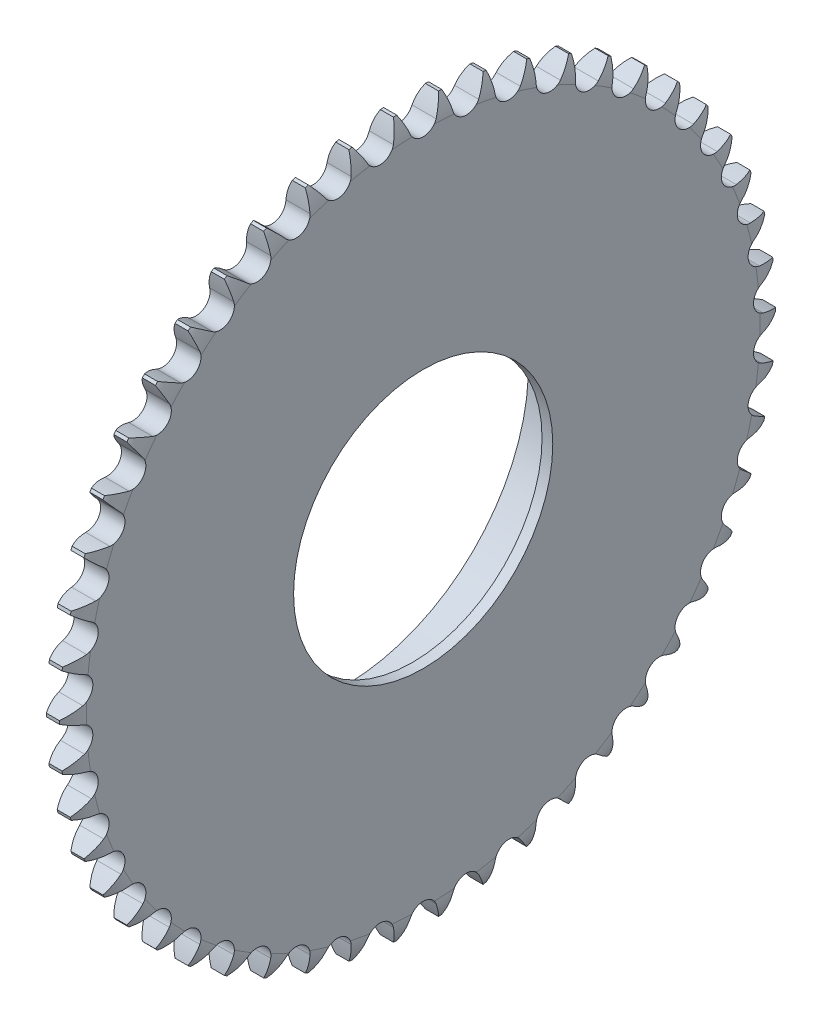
SolidWorks part; units mm, degrees
ref_plane "Plane1" through (0, 0, 0) normal (0, 0, 1) x (1, 0, 0)
ref_plane "Plane2" through (0, 0, 0) normal (0, 1, 0) x (1, 0, 0)
ref_plane "Plane3" through (0, 0, 0) normal (1, 0, 0) x (0, 0, -1)
sketch "Clipboard" plane through (0, 0, 0) normal (0, 1, 0) x (1, 0, 0)
  line L0 (0, 0) -> (10.2043, -12.161)
  line L1 (-15, 0) -> (100, 0) construction
  line L2 (0, 0) -> (-1.3675, 1.5456)
  line L3 (0, 0) -> (-14.8288, 5.6677)
  line L4 (0, 0) -> (1.9926, 2.3747)
  line L5 (0, 0) -> (-23.4238, -8.7364)
  line L6 (0, 0) -> (-7.4026, -4.9946)
  line L7 (-1.3675, 1.5456) -> (14.3658, 20.9747)
  line L8 (-76.2, 38.1) -> (-69.8, 38.1)
  line L9 (-73.5462, 42.5082) -> (-72.9534, 42.6013)
  line L10 (-74, 16.6356) -> (-55.89, 16.6356)
  circle A0 centre (0, 0) radius 5.08
  circle A1 centre (0, 0) radius 60
  circle A2 centre (0, 0) radius 60
  dimension "Num_teeth" = 50
  dimension "Thickness" = 8.93
sketch "BasProSke" plane through (0, 0, 0) normal (0, 1, 0) x (1, 0, 0)
  line L0 (-10, 0) -> (60, 0) construction
  line L1 (0, 0) -> (0, 123.4271)
  line L2 (0, 0) -> (8.93, 0)
  line L3 (8.93, 0) -> (8.93, 123.4271)
  line L4 (6.8662, 131.2543) -> (2.0637, 131.2543)
  arc A0 (0, 123.4271) -> (2.0637, 131.2543) centre (15.875, 123.4271) cw
  arc A1 (8.93, 123.4271) -> (6.8662, 131.2543) centre (-6.945, 123.4271) ccw
  dimension "D1" = 15.875
  dimension "Thickness" = 8.93
  dimension "Diameter" = 262.5085
revolve "Base-Revolve" add sketch "BasProSke" angle 360 about L0
sketch "TooCutSke" plane through (0, 0, 0) normal (1, 0, 0) x (0, 0, -1)
  line L0 (0, 126.4632) -> (4.7932, 124.6328) construction
  line L1 (0, 0) -> (0, 107) construction
  line L2 (0, 126.4632) -> (-10, 126.4632) construction
  line L3 (0, 126.4632) -> (-4.7932, 124.6328) construction
  arc A0 (4.7932, 124.6328) -> (7.9038, 131.517) centre (64.0203, 102.0162) cw
  arc A1 (4.7932, 124.6328) -> (-4.7932, 124.6328) centre (0, 126.4632) cw
  arc A2 (-4.7932, 124.6328) -> (-7.9038, 131.517) centre (-64.0203, 102.0162) ccw
  arc A3 (7.9038, 131.517) -> (-7.9038, 131.517) centre (0, 0) ccw
extrude "ToothCut" cut sketch "TooCutSke" along normal through all
pattern_circular "TeethCuts" count 50 every 7.2 about axis through (-10, 0, 0) along (1, 0, 0) of "ToothCut"
sketch "HubNeaOneSke" plane through (0, 0, 0) normal (-1, 0, 0) x (0, 0, 1)
  circle A0 centre (0, 0) radius 75
  dimension "D1" = 150
extrude "HubNearOne" add sketch "HubNeaOneSke" along normal blind 20
fillet "HubNearOneFillet" radius 0.6 1 edges at (0, 0, -75)
sketch "HubNeaBotSke" plane through (0, 0, 0) normal (-1, 0, 0) x (0, 0, 1)
  circle A0 centre (0, 0) radius 60
  dimension "Diameter" = 120
extrude "HubNearBoth" [suppressed] add sketch "HubNeaBotSke" along normal blind 8.0352
fillet "HubNearBothFillet" [suppressed] radius 0.6
ref_plane "FarPln" through (8.93, 0, 0) normal (1, 0, 0) x (0, 0, -1)
sketch "HubFarSke" plane through (8.93, 0, 0) normal (1, 0, 0) x (0, 0, -1)
  circle A0 centre (0, 0) radius 60
  dimension "Diameter" = 120
extrude "HubFar" [suppressed] add sketch "HubFarSke" along normal blind 8.0352
fillet "HubFarFillet" [suppressed] radius 0.6
sketch "BorSke" plane through (0, 0, 0) normal (1, 0, 0) x (0, 0, -1)
  circle A0 centre (0, 0) radius 47.5
  dimension "Diameter" = 95
extrude "Bore" cut sketch "BorSke" along normal mid plane 50.001
sketch "KeySke" plane through (0, 0, 0) normal (1, 0, 0) x (0, 0, -1)
  line L0 (-14, 0) -> (-14, 53.9)
  line L1 (-14, 53.9) -> (14, 53.9)
  line L2 (14, 53.9) -> (14, 0)
  line L3 (0, 0) -> (0, 34) construction
  line L4 (-14, 0) -> (14, 0)
  dimension "Width" = 28
extrude "Keyway" [suppressed] cut sketch "KeySke" along normal mid plane 50.001
pattern_circular "Keyway2" [suppressed] count 2 every 90 about axis through (-10, 0, 0) along (1, 0, 0) reverse direction yes
sketch "Schizzo1" plane through (-20, 0, 0) normal (-1, 0, 0) x (0, 0, 1)
  circle A0 centre (0, 0) radius 67.5
extrude "Taglio-Estrusione1" cut sketch "Schizzo1" against normal blind 25
equation "' \"Pitch@Clipboard\" = 12.7"
equation "' \"Num_strands@Clipboard\" = 1"
equation "' \"Num_teeth@Clipboard\" = 9"
equation "' \"Hub_dia@Clipboard\" = 50"
equation "' \"Overall_len@Clipboard\" = 3"
equation "' \"Diameter@BorSke\" = 12"
equation "' \"T_dim@Clipboard\" = 1"
equation "' \"Width@KeySke\" = 2"
equation "' \"Dr@Clipboard\" = 8.51"
equation "' \"Face_width@Clipboard\" = 7.2"
equation "' \"Side_radius@Clipboard\" = 12.7"
equation "' \"Side_relief@Clipboard\" = 1.27"
equation "' \"Transv_pitch@Clipboard\" = 13.92"
equation "' \"Show_teeth@Clipboard\" = 9"
equation "' \"Fillet_rad@Clipboard\" = 0.6"
equation "' \"Plate_wid@Clipboard\" = 11.8"
equation "\"Num_teeth@Clipboard\" = int( \"Num_teeth@Clipboard\" )"
equation "\"Num_teeth@Clipboard\" = ((sgn( \"Num_teeth@Clipboard\" - 5.0)+1)*( \"Num_teeth@Clipboard\" - 5.0))/2 +5.0"
equation "\"Num_teeth@Clipboard\" = ((sgn( \"Num_teeth@Clipboard\" - 200.0)-1)*( \"Num_teeth@Clipboard\" - 200.0))/-2 +200.0"
equation "\"MHD@Clipboard\" = \"Pitch@Clipboard\" * (1.0 / tan(3.14159265 / \"Num_teeth@Clipboard\" )) - 1.04 * \"Plate_wid@Clipboard\" - 0.76"
equation "\"Thickness@Clipboard\"  = \"Face_width@Clipboard\" + (\"Num_strands@Clipboard\" - 1) * \"Transv_pitch@Clipboard\""
equation "\"OAL@Clipboard\" = \"Thickness@Clipboard\" + 2 * \"Fillet_rad@Clipboard\" + 1"
equation "\"MHD@Clipboard\" = ((sgn( \"MHD@Clipboard\" - \"Hub_dia@Clipboard\" )-1)*( \"MHD@Clipboard\" - \"Hub_dia@Clipboard\" ))/-2+ \"Hub_dia@Clipboard\""
equation "\"OAL@Clipboard\" = ((sgn( \"OAL@Clipboard\" - \"Overall_len@Clipboard\" )+1)*( \"OAL@Clipboard\" - \"Overall_len@Clipboard\" ))/2 + \"Overall_len@Clipboard\" + 0.0005"
equation "\"Num_teeth@TeethCuts\" = int( \"Show_teeth@Clipboard\" ) + 1"
equation "\"Num_teeth@TeethCuts\" = ((sgn( \"Num_teeth@TeethCuts\" - \"Num_teeth@Clipboard\" )-1)*( \"Num_teeth@TeethCuts\" - \"Num_teeth@Clipboard\" ))/-2+ \"Num_teeth@Clipboard\""
equation "\"Num_teeth@TeethCuts\" = ((sgn( \"Num_teeth@TeethCuts\" - 2.0)+1)*( \"Num_teeth@TeethCuts\" - 2.0))/2 +2.0"
equation "\"Angle@TeethCuts\" = 360.0 / \"Num_teeth@Clipboard\""
equation "\"Seat_radius@TooCutSke\" = ( \"Pitch@Clipboard\" / 2.0) / sin(3.14159265 / \"Num_teeth@Clipboard\" ) - \"Dr@Clipboard\" / 2.0 + \"Dr@Clipboard\" * 0.505"
equation "\"R1@TooCutSke\"  = \"Dr@Clipboard\" * 0.505"
equation "\"X@TooCutSke\" = 140.0 - (90.0 / \"Num_teeth@Clipboard\")"
equation "\"R2@TooCutSke\" = 0.12 * \"Dr@Clipboard\" * ( \"Num_teeth@Clipboard\" + 2.0)"
equation "\"Overcut@TooCutSke\" = 0.5 + 0.625 * \"Pitch@Clipboard\" - 0.5 * \"Dr@Clipboard\"  +  \"Pitch@Clipboard\" / 2.0 / sin(3.14159265 / \"Num_teeth@Clipboard\" )"
equation "\"Diameter@BasProSke\" = 2.0 * ( 0.625 * \"Pitch@Clipboard\" - 0.5 * \"Dr@Clipboard\"  +  \"Pitch@Clipboard\" / 2.0 / sin(3.14159265 / \"Num_teeth@Clipboard\" ))"
equation "\"Thickness@BasProSke\"  = \"Thickness@Clipboard\""
equation "\"G1@BasProSke\" =  \"Side_relief@Clipboard\""
equation "\"G2@BasProSke\" =  \"Side_relief@Clipboard\""
equation "\"D1@BasProSke\" =  \"Side_radius@Clipboard\""
equation "\"Diameter@HubNeaBotSke\" = \"MHD@Clipboard\""
equation "\"Length@HubNearBoth\" = ( \"OAL@Clipboard\" - \"Thickness@BasProSke\" ) / 2.0"
equation "\"D1@HubNearOneFillet\" = \"Fillet_rad@Clipboard\""
equation "\"D1@HubNearBothFillet\" = \"Fillet_rad@Clipboard\""
equation "\"Thickness@FarPln\" = \"Thickness@BasProSke\""
equation "\"Diameter@HubFarSke\" = \"MHD@Clipboard\""
equation "\"Length@HubFar\" = ( \"OAL@Clipboard\" - \"Thickness@BasProSke\" ) / 2.0"
equation "\"D1@HubFarFillet\" = \"Fillet_rad@Clipboard\""
equation "\"D1@Bore\" = \"OAL@Clipboard\" * 2.0"
equation "\"D1@Keyway\" = \"OAL@Clipboard\" * 2.0"
equation "\"Offset@KeySke\" = \"T_dim@Clipboard\" + \"Diameter@BorSke\" / 2.0"
